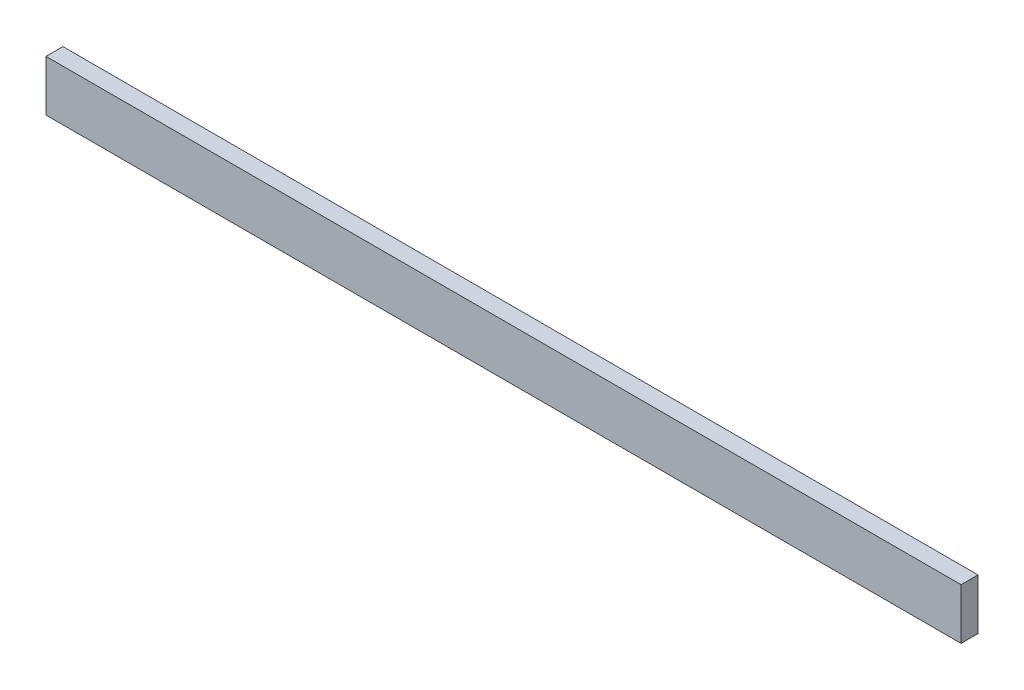
SolidWorks part; units mm, degrees
ref_plane "前视基准面" through (0, 0, 0) normal (0, 0, 1) x (1, 0, 0)
ref_plane "上视基准面" through (0, 0, 0) normal (0, 1, 0) x (1, 0, 0)
ref_plane "右视基准面" through (0, 0, 0) normal (1, 0, 0) x (0, 0, -1)
sketch "草图1" plane through (0, 0, 0) normal (0, 0, 1) x (1, 0, 0)
  line L1 (-27, -1.5) -> (27, -1.5)
  line L2 (-27, -1.5) -> (-27, 1.5)
  line L3 (-27, 1.5) -> (27, 1.5)
  line L4 (27, -1.5) -> (27, 1.5)
  line L5 (-27, -1.5) -> (27, 1.5) construction
  line L6 (-27, 1.5) -> (27, -1.5) construction
  point P0 (0, 0)
  dimension "D1" = 54
  dimension "D2" = 3
extrude "凸台-拉伸1" add sketch "草图1" along normal blind 1
